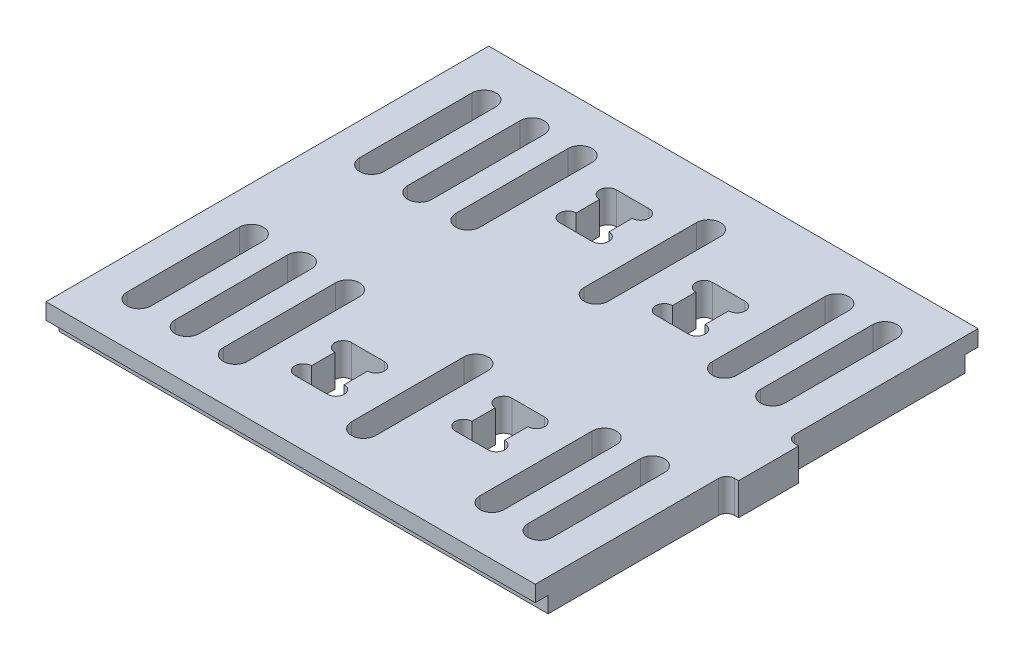
SolidWorks part; units mm, degrees
material "PE High Density"
ref_plane "Front Plane" through (0, 0, 0) normal (0, 0, 1) x (1, 0, 0)
ref_plane "Top Plane" through (0, 0, 0) normal (0, 1, 0) x (1, 0, 0)
ref_plane "Right Plane" through (0, 0, 0) normal (1, 0, 0) x (0, 0, -1)
sketch "Sketch1" plane through (0, 0, 0) normal (1, 0, 0) x (0, 0, -1)
  line L1 (-87.63, -6.35) -> (87.63, -6.35)
  line L2 (-87.63, -6.35) -> (-87.63, 6.35)
  line L3 (-87.63, 6.35) -> (87.63, 6.35)
  line L4 (87.63, -6.35) -> (87.63, 6.35)
  line L5 (-87.63, -6.35) -> (87.63, 6.35) construction
  line L6 (-87.63, 6.35) -> (87.63, -6.35) construction
  point P0 (0, 0)
  dimension "D1" = 175.26
  dimension "D2" = 12.7
extrude "Boss-Extrude1" add sketch "Sketch1" along normal mid plane 193.675
sketch "Sketch2" plane through (96.8375, 0, 0) normal (1, 0, 0) x (0, 0, -1)
  line L0 (87.63, 6.35) -> (-87.63, 6.35) construction
  line L1 (-87.63, -6.35) -> (-82.55, -6.35)
  line L2 (-87.63, -6.35) -> (-87.63, 0)
  line L3 (-87.63, 0) -> (-82.55, 0)
  line L4 (-82.55, -6.35) -> (-82.55, 0)
  line L5 (87.63, -6.35) -> (82.55, -6.35)
  line L6 (87.63, -6.35) -> (87.63, 0)
  line L7 (87.63, 0) -> (82.55, 0)
  line L8 (82.55, -6.35) -> (82.55, 0)
  dimension "D1" = 6.35
  dimension "D2" = 165.1
extrude "Cut-Extrude1" cut sketch "Sketch2" against normal through all
sketch "Sketch3" plane through (0, 6.35, 0) normal (0, 1, 0) x (1, 0, 0)
  line L0 (96.8375, 87.63) -> (96.8375, -87.63) construction
  line L1 (28.448, -28.448) -> (41.402, -28.448)
  line L2 (28.448, -35.052) -> (28.448, -44.323)
  line L3 (28.448, -50.927) -> (41.402, -50.927)
  line L4 (41.402, -35.052) -> (41.402, -44.323)
  line L17 (-22.352, -41.148) -> (-9.398, -41.148)
  line L18 (-22.352, -47.752) -> (-22.352, -57.023)
  line L19 (-22.352, -63.627) -> (-9.398, -63.627)
  line L20 (-9.398, -47.752) -> (-9.398, -57.023)
  line L21 (0, 0) -> (96.8375, 0) construction
  line L22 (-9.398, 47.752) -> (-9.398, 57.023)
  line L23 (-22.352, 63.627) -> (-9.398, 63.627)
  line L24 (-22.352, 47.752) -> (-22.352, 57.023)
  line L25 (-22.352, 41.148) -> (-9.398, 41.148)
  line L26 (41.402, 35.052) -> (41.402, 44.323)
  line L27 (28.448, 50.927) -> (41.402, 50.927)
  line L28 (28.448, 35.052) -> (28.448, 44.323)
  line L29 (28.448, 28.448) -> (41.402, 28.448)
  arc A0 (28.448, -28.448) -> (28.448, -35.052) centre (28.448, -31.75) ccw
  arc A1 (28.448, -44.323) -> (28.448, -50.927) centre (28.448, -47.625) ccw
  arc A2 (41.402, -50.927) -> (41.402, -44.323) centre (41.402, -47.625) ccw
  arc A3 (41.402, -35.052) -> (41.402, -28.448) centre (41.402, -31.75) ccw
  arc A16 (-22.352, -41.148) -> (-22.352, -47.752) centre (-22.352, -44.45) ccw
  arc A17 (-22.352, -57.023) -> (-22.352, -63.627) centre (-22.352, -60.325) ccw
  arc A18 (-9.398, -63.627) -> (-9.398, -57.023) centre (-9.398, -60.325) ccw
  arc A19 (-9.398, -47.752) -> (-9.398, -41.148) centre (-9.398, -44.45) ccw
  arc A20 (-9.398, 47.752) -> (-9.398, 41.148) centre (-9.398, 44.45) cw
  arc A21 (-9.398, 63.627) -> (-9.398, 57.023) centre (-9.398, 60.325) cw
  arc A22 (-22.352, 57.023) -> (-22.352, 63.627) centre (-22.352, 60.325) cw
  arc A23 (-22.352, 41.148) -> (-22.352, 47.752) centre (-22.352, 44.45) cw
  arc A24 (41.402, 35.052) -> (41.402, 28.448) centre (41.402, 31.75) cw
  arc A25 (41.402, 50.927) -> (41.402, 44.323) centre (41.402, 47.625) cw
  arc A26 (28.448, 44.323) -> (28.448, 50.927) centre (28.448, 47.625) cw
  arc A27 (28.448, 28.448) -> (28.448, 35.052) centre (28.448, 31.75) cw
  point P11 (34.925, -28.448)
  point P18 (41.402, -39.6875)
  point P19 (96.8375, 0)
  point P32 (-9.398, -52.3875)
  dimension "D3" = 6.604
  dimension "D6" = 3.302
  dimension "D1" = 12.954
  dimension "D2" = 22.479
  dimension "D4" = 61.9125
  dimension "D5" = 39.6875
  dimension "D7" = 22.479
  dimension "D8" = 12.954
  dimension "D9" = 52.3875
  dimension "D10" = 50.8
extrude "Cut-Extrude2" cut sketch "Sketch3" against normal through all
sketch "Sketch4" plane through (0, 6.35, 0) normal (0, 1, 0) x (1, 0, 0)
  line L0 (60.325, -68.2625) -> (60.325, -23.8125) construction
  line L1 (55.5625, -68.2625) -> (55.5625, -23.8125)
  line L2 (65.0875, -68.2625) -> (65.0875, -23.8125)
  line L3 (60.325, 23.8125) -> (60.325, 68.2625) construction
  line L4 (55.5625, 23.8125) -> (55.5625, 68.2625)
  line L5 (65.0875, 23.8125) -> (65.0875, 68.2625)
  line L6 (79.375, 68.2625) -> (79.375, 23.8125) construction
  line L7 (84.1375, 68.2625) -> (84.1375, 23.8125)
  line L8 (74.6125, 68.2625) -> (74.6125, 23.8125)
  line L9 (79.375, -23.8125) -> (79.375, -68.2625) construction
  line L10 (84.1375, -23.8125) -> (84.1375, -68.2625)
  line L11 (74.6125, -23.8125) -> (74.6125, -68.2625)
  line L12 (96.8375, 87.63) -> (96.8375, -87.63) construction
  line L13 (-79.375, -68.2625) -> (-79.375, -23.8125) construction
  line L14 (-84.1375, -68.2625) -> (-84.1375, -23.8125)
  line L15 (-74.6125, -68.2625) -> (-74.6125, -23.8125)
  line L16 (-79.375, 23.8125) -> (-79.375, 68.2625) construction
  line L17 (-84.1375, 23.8125) -> (-84.1375, 68.2625)
  line L18 (-74.6125, 23.8125) -> (-74.6125, 68.2625)
  line L19 (-96.8375, 87.63) -> (-96.8375, -87.63) construction
  line L20 (-60.325, -68.2625) -> (-60.325, -23.8125) construction
  line L21 (-65.0875, -68.2625) -> (-65.0875, -23.8125)
  line L22 (-55.5625, -68.2625) -> (-55.5625, -23.8125)
  line L23 (-60.325, 23.8125) -> (-60.325, 68.2625) construction
  line L24 (-65.0875, 23.8125) -> (-65.0875, 68.2625)
  line L25 (-55.5625, 23.8125) -> (-55.5625, 68.2625)
  line L26 (-41.275, -68.2625) -> (-41.275, -23.8125) construction
  line L27 (-46.0375, -68.2625) -> (-46.0375, -23.8125)
  line L28 (-36.5125, -68.2625) -> (-36.5125, -23.8125)
  line L29 (-41.275, 23.8125) -> (-41.275, 68.2625) construction
  line L30 (-46.0375, 23.8125) -> (-46.0375, 68.2625)
  line L31 (-36.5125, 23.8125) -> (-36.5125, 68.2625)
  line L32 (-79.375, -68.2625) -> (-60.325, -68.2625) construction
  line L33 (9.525, -68.2625) -> (9.525, -23.8125) construction
  line L34 (4.7625, -68.2625) -> (4.7625, -23.8125)
  line L35 (14.2875, -68.2625) -> (14.2875, -23.8125)
  line L36 (9.525, 23.8125) -> (9.525, 68.2625) construction
  line L37 (4.7625, 23.8125) -> (4.7625, 68.2625)
  line L38 (14.2875, 23.8125) -> (14.2875, 68.2625)
  line L39 (28.448, -35.052) -> (28.448, -44.323) construction
  line L40 (-9.398, -57.023) -> (-9.398, -47.752) construction
  arc A0 (55.5625, -68.2625) -> (65.0875, -68.2625) centre (60.325, -68.2625) ccw
  arc A1 (65.0875, -23.8125) -> (55.5625, -23.8125) centre (60.325, -23.8125) ccw
  arc A2 (55.5625, 23.8125) -> (65.0875, 23.8125) centre (60.325, 23.8125) ccw
  arc A3 (65.0875, 68.2625) -> (55.5625, 68.2625) centre (60.325, 68.2625) ccw
  arc A4 (84.1375, 68.2625) -> (74.6125, 68.2625) centre (79.375, 68.2625) ccw
  arc A5 (74.6125, 23.8125) -> (84.1375, 23.8125) centre (79.375, 23.8125) ccw
  arc A6 (84.1375, -23.8125) -> (74.6125, -23.8125) centre (79.375, -23.8125) ccw
  arc A7 (74.6125, -68.2625) -> (84.1375, -68.2625) centre (79.375, -68.2625) ccw
  arc A8 (-84.1375, -68.2625) -> (-74.6125, -68.2625) centre (-79.375, -68.2625) ccw
  arc A9 (-74.6125, -23.8125) -> (-84.1375, -23.8125) centre (-79.375, -23.8125) ccw
  arc A10 (-84.1375, 23.8125) -> (-74.6125, 23.8125) centre (-79.375, 23.8125) ccw
  arc A11 (-74.6125, 68.2625) -> (-84.1375, 68.2625) centre (-79.375, 68.2625) ccw
  arc A12 (-65.0875, -68.2625) -> (-55.5625, -68.2625) centre (-60.325, -68.2625) ccw
  arc A13 (-55.5625, -23.8125) -> (-65.0875, -23.8125) centre (-60.325, -23.8125) ccw
  arc A14 (-65.0875, 23.8125) -> (-55.5625, 23.8125) centre (-60.325, 23.8125) ccw
  arc A15 (-55.5625, 68.2625) -> (-65.0875, 68.2625) centre (-60.325, 68.2625) ccw
  arc A16 (-46.0375, -68.2625) -> (-36.5125, -68.2625) centre (-41.275, -68.2625) ccw
  arc A17 (-36.5125, -23.8125) -> (-46.0375, -23.8125) centre (-41.275, -23.8125) ccw
  arc A18 (-46.0375, 23.8125) -> (-36.5125, 23.8125) centre (-41.275, 23.8125) ccw
  arc A19 (-36.5125, 68.2625) -> (-46.0375, 68.2625) centre (-41.275, 68.2625) ccw
  arc A20 (4.7625, -68.2625) -> (14.2875, -68.2625) centre (9.525, -68.2625) ccw
  arc A21 (14.2875, -23.8125) -> (4.7625, -23.8125) centre (9.525, -23.8125) ccw
  arc A22 (4.7625, 23.8125) -> (14.2875, 23.8125) centre (9.525, 23.8125) ccw
  arc A23 (14.2875, 68.2625) -> (4.7625, 68.2625) centre (9.525, 68.2625) ccw
  point P2 (60.325, -46.0375)
  point P7 (60.325, 46.0375)
  point P14 (79.375, 46.0375)
  point P21 (79.375, -46.0375)
  point P30 (-79.375, -46.0375)
  point P33 (96.8375, 0)
  point P38 (-79.375, 46.0375)
  point P51 (-60.325, -46.0375)
  point P56 (-60.325, 46.0375)
  point P65 (-41.275, -46.0375)
  point P70 (-41.275, 46.0375)
  point P79 (9.525, -46.0375)
  point P84 (9.525, 46.0375)
  point P91 (0, 0)
  point P92 (0, 0)
  point P93 (0, 0)
  point P98 (0, 0)
  point P99 (0, 0)
  point P100 (0, 0)
  dimension "D1" = 4.7625
  dimension "D2" = 44.45
  dimension "D3" = 92.075
  dimension "D4" = 46.0375
  dimension "D6" = 19.05
  dimension "D7" = 17.4625
  dimension "D5" = 17.4625
  dimension "D9" = 19.05
  dimension "D8" = 3
extrude "Cut-Extrude3" cut sketch "Sketch4" against normal through all
sketch "Sketch5" plane through (0, 6.35, 0) normal (0, 1, 0) x (1, 0, 0)
  line L0 (96.8375, 87.63) -> (96.8375, -87.63) construction
  line L1 (96.8375, 11.9063) -> (101.6, 11.9062)
  line L2 (96.8375, 11.9063) -> (96.8375, -11.9063)
  line L3 (96.8375, -11.9063) -> (101.6, -11.9063)
  line L4 (101.6, 11.9062) -> (101.6, -11.9063)
  point P6 (101.6, 0)
  dimension "D1" = 23.8125
  dimension "D2" = 4.7625
extrude "Boss-Extrude2" add sketch "Sketch5" against normal up to surface (12.7 mm away) up to face at (-79.375, -6.35, -46.0375)
fillet "Fillet1" radius 3.175 2 edges at (96.8375, 0, -11.9063) (96.8375, 0, 11.9063)
equation "\"D1@Boss-Extrude1\"=7.66629343in "
equation "\"D5@Sketch3\"=4.125/2-.5"
equation "\"D4@Sketch4\"=\"D3@Sketch4\"/2"
equation "\"D6@Sketch3\"=\"D3@Sketch3\"/2"
equation "\"D7@Sketch3\"=\"D2@Sketch3\""
equation "\"D8@Sketch3\"=\"D1@Sketch3\""
equation "\"D9@Sketch3\"=\"D5@Sketch3\"+.5"
equation "\"D7@Sketch4\"=\"D5@Sketch4\""
